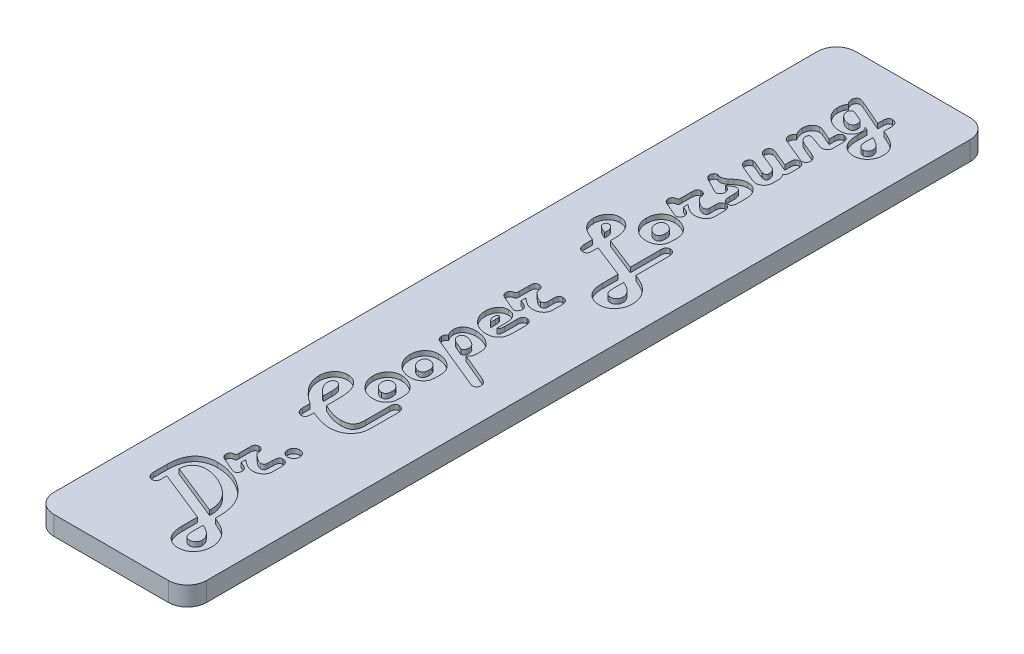
SolidWorks part; units mm, degrees
ref_plane "Front Plane" through (0, 0, 0) normal (0, 0, 1) x (1, 0, 0)
ref_plane "Top Plane" through (0, 0, 0) normal (0, 1, 0) x (1, 0, 0)
ref_plane "Right Plane" through (0, 0, 0) normal (1, 0, 0) x (0, 0, -1)
sketch "Sketch1" plane through (0, 0, 0) normal (0, 0, 1) x (1, 0, 0)
  line L0 (0, 1.5875) -> (0, -1.5875)
  line L1 (-12.7, 0) -> (12.7, 0) construction
  point P6 (0, 0)
  dimension "Width" = 25.4
  dimension "Thk" = 3.175
sketch "Sketch2" plane through (0, 0, 0) normal (1, 0, 0) x (0, 0, -1)
  line L0 (66.675, 0) -> (-66.675, 0)
  point P4 (0, 0)
  dimension "Length" = 133.35
sketch "Sketch3" plane through (0, 0, 0) normal (0, 0, 1) x (1, 0, 0)
  line L1 (12.7, 1.5875) -> (-12.7, 1.5875)
  line L2 (12.7, 1.5875) -> (12.7, -1.5875)
  line L3 (12.7, -1.5875) -> (-12.7, -1.5875)
  line L4 (-12.7, 1.5875) -> (-12.7, -1.5875)
  line L5 (12.7, 1.5875) -> (-12.7, -1.5875) construction
  line L6 (12.7, -1.5875) -> (-12.7, 1.5875) construction
  point P0 (0, 0)
extrude "Boss-Extrude1" add sketch "Sketch3" along normal up to vertex (66.675 mm away) and the other way up to vertex (66.675 mm away) up to point (0, 0, 66.675) other way up to point (0, 0, -66.675)
sketch "Sketch5" plane through (0, 1.5875, 0) normal (0, 1, 0) x (1, 0, 0)
  line L0 (-9.525, 66.675) -> (9.525, 66.675)
  line L1 (12.7, 63.5) -> (12.7, -63.5)
  line L2 (9.525, -66.675) -> (-9.525, -66.675)
  line L3 (-12.7, -63.5) -> (-12.7, 63.5)
  arc A0 (9.525, -66.675) -> (12.7, -63.5) centre (9.525, -63.5) ccw construction
  arc A1 (9.525, -66.675) -> (12.7, -63.5) centre (9.525, -63.5) ccw
  arc A2 (-12.7, -63.5) -> (-9.525, -66.675) centre (-9.525, -63.5) ccw construction
  arc A3 (-12.7, -63.5) -> (-9.525, -66.675) centre (-9.525, -63.5) ccw
  arc A4 (12.7, 63.5) -> (9.525, 66.675) centre (9.525, 63.5) ccw construction
  arc A5 (12.7, 63.5) -> (9.525, 66.675) centre (9.525, 63.5) ccw
  arc A6 (-9.525, 66.675) -> (-12.7, 63.5) centre (-9.525, 63.5) ccw construction
  arc A7 (-9.525, 66.675) -> (-12.7, 63.5) centre (-9.525, 63.5) ccw
extrude "Cut-Extrude2" cut sketch "Sketch5" against normal through all flip side to cut
sketch "Sketch4" plane through (0, 1.5875, 0) normal (0, 1, 0) x (1, 0, 0)
  line L0 (0, 0) -> (2.54, 0) construction
  line L1 (2.54, -66.675) -> (2.54, 66.675) construction
  line L2 (9.525, 66.675) -> (-9.525, 66.675) construction
  text T0 "Dr. Cooper Lorsung" font "Harlow Solid Italic" height 10
  point P8 (2.54, 0)
  dimension "D1" = 2.54
extrude "Cut-Extrude1" cut sketch "Sketch4" against normal blind 0.7937
